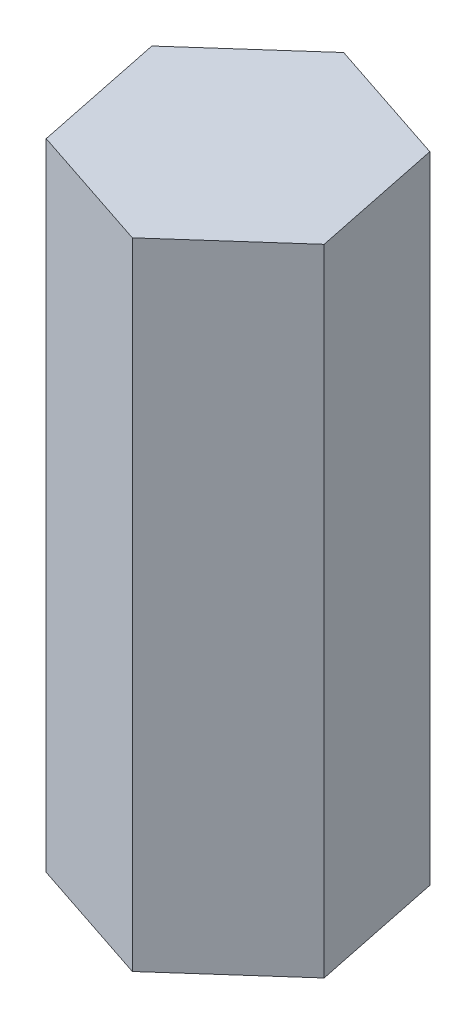
SolidWorks part; units mm, degrees
ref_plane "Front Plane" through (0, 0, 0) normal (0, 0, 1) x (1, 0, 0)
ref_plane "Top Plane" through (0, 0, 0) normal (0, 1, 0) x (1, 0, 0)
ref_plane "Right Plane" through (0, 0, 0) normal (1, 0, 0) x (0, 0, -1)
sketch "Sketch1" plane through (0, 0, 0) normal (0, 1, 0) x (1, 0, 0)
  line L1 (5.4803, 4.8713) -> (-1.4786, 7.1817)
  line L2 (-1.4786, 7.1817) -> (-6.9588, 2.3104)
  line L3 (-6.9588, 2.3104) -> (-5.4803, -4.8713)
  line L4 (-5.4803, -4.8713) -> (1.4786, -7.1817)
  line L5 (1.4786, -7.1817) -> (6.9588, -2.3104)
  line L6 (6.9588, -2.3104) -> (5.4803, 4.8713)
  circle A0 centre (0, 0) radius 6.35 construction
  dimension "D1" = 12.7
extrude "Boss-Extrude1" add sketch "Sketch1" along normal blind 34.29
